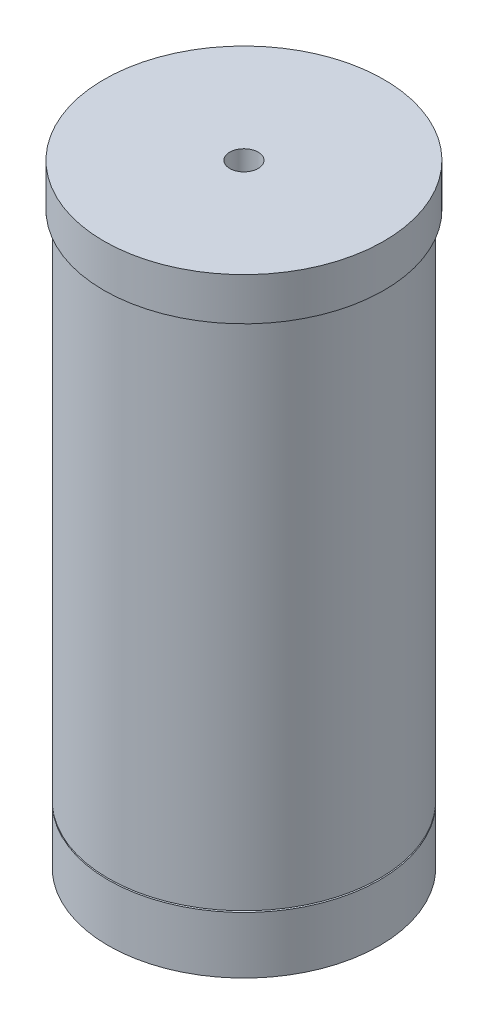
SolidWorks part; units mm, degrees
other "Bulkhead"
other "Tray"
other "Body"
other "Lid"
ref_plane "Front Plane" through (0, 0, 0) normal (0, 0, 1) x (1, 0, 0)
ref_plane "Top Plane" through (0, 0, 0) normal (0, 1, 0) x (1, 0, 0)
ref_plane "Right Plane" through (0, 0, 0) normal (1, 0, 0) x (0, 0, -1)
sketch "Sketch1" plane through (0, 0, 0) normal (0, 1, 0) x (1, 0, 0)
  circle A0 centre (0, 0) radius 47.75
  circle A1 centre (0, 0) radius 5
  circle A9 centre (-23.3345, 23.3345) radius 6
  circle A11 centre (-23.3345, 23.3345) radius 11.5
  circle A12 centre (-23.3345, 23.3345) radius 8.5
  circle A27 centre (8.541, 31.8756) radius 6
  circle A28 centre (8.541, 31.8756) radius 8.5
  circle A30 centre (8.541, 31.8756) radius 11.5
  circle A31 centre (31.8756, 8.541) radius 6
  circle A33 centre (31.8756, 8.541) radius 8.5
  circle A34 centre (31.8756, 8.541) radius 11.5
  circle A36 centre (23.3345, -23.3345) radius 6
  circle A37 centre (23.3345, -23.3345) radius 8.5
  circle A39 centre (23.3345, -23.3345) radius 11.5
  circle A40 centre (-8.541, -31.8756) radius 6
  circle A41 centre (-8.541, -31.8756) radius 8.5
  circle A42 centre (-8.541, -31.8756) radius 11.5
  circle A44 centre (-31.8756, -8.541) radius 6
  circle A45 centre (-31.8756, -8.541) radius 8.5
  circle A46 centre (-31.8756, -8.541) radius 11.5
  point P22 (0, 0)
  point P43 (0, 0)
  point P56 (0, 0)
  dimension "D1" = 95.5
  dimension "D2" = 10
  dimension "D3" = 33
  dimension "D5" = 2.5
  dimension "D4" = 3
  dimension "D6" = 6
extrude "Boss-Extrude1" add sketch "Sketch1" along normal blind 45 contours A0 A46 A42 A39 A34 A30 A11 A1 | A39 A37 | A37 A36 | A34 A33 | A33 A31 | A42 A41 | A41 A40 | A46 A45 | A45 A44 | A11 A12 | A12 A9 | A30 A28 | A28 A27
extrude "Cut-Extrude1" cut sketch "Sketch1<3>" along normal blind 5 contours A42 A41 | A46 A45 | A11 A12 | A30 A28 | A34 A33 | A39 A37
sketch "Sketch1<3>" plane through (0, 0, 0) normal (0, 1, 0) x (1, 0, 0) same geometry as "Sketch1"
sketch "Sketch3" plane through (0, 45, 0) normal (0, 1, 0) x (1, 0, 0)
  circle A0 centre (0, 0) radius 47.75
  circle A1 centre (0, 0) radius 5
  dimension "D1" = 95.5
extrude "Boss-Extrude2" add sketch "Sketch3" along normal blind 10
sketch "Sketch6" plane through (0, 55, 0) normal (0, 1, 0) x (1, 0, 0)
  line L4 (-10, 34.4976) -> (-10, -34.4976)
  line L6 (-15, 39.4976) -> (-15, -39.4976)
  line L8 (15, 39.4976) -> (15, -39.4976)
  line L10 (10, 34.4976) -> (10, -34.4976)
  line L12 (-9.5, 33.9976) -> (-9.5, -33.9976)
  line L14 (9.5, 33.9976) -> (9.5, -33.9976)
  line L16 (-15, 39.4976) -> (15, 39.4976) construction
  line L17 (-15, -39.4976) -> (15, -39.4976) construction
  line L18 (-10, -34.4976) -> (10, -34.4976) construction
  line L19 (-10, 34.4976) -> (10, 34.4976) construction
  line L20 (-9.5, -33.9976) -> (9.5, -33.9976) construction
  line L21 (-9.5, 33.9976) -> (9.5, 33.9976) construction
  line L22 (-5.5, 30.813) -> (-5.5, -30.813)
  line L23 (5.5, 30.813) -> (5.5, -30.813)
  circle A0 centre (0, 0) radius 49.28
  circle A1 centre (0, 0) radius 42.5
  arc A4 (-15, -39.4976) -> (15, -39.4976) centre (0, 0) ccw
  arc A5 (-10, -34.4976) -> (10, -34.4976) centre (0, 0) ccw
  arc A6 (10, 34.4976) -> (-10, 34.4976) centre (0, 0) ccw
  arc A7 (15, 39.4976) -> (-15, 39.4976) centre (0, 0) ccw
  arc A8 (-9.5, -33.9976) -> (9.5, -33.9976) centre (0, 0) ccw
  arc A9 (9.5, 33.9976) -> (-9.5, 33.9976) centre (0, 0) ccw
  arc A10 (-5.5, -30.813) -> (5.5, -30.813) centre (0, 0) ccw
  arc A11 (5.5, 30.813) -> (-5.5, 30.813) centre (0, 0) ccw
  circle M8 centre (0, 0) radius 47.75
  dimension "D1" = 85
  dimension "D2" = 84.5
  dimension "D4" = 30
  dimension "D6" = 4
  dimension "D3" = 5
  dimension "D5" = 0.5
extrude "Boss-Extrude6" add sketch "Sketch6" along normal blind 125 separate body contours L8 A7 L6 A4 A6 L10 A5 L4 | A1 M8 region at (0, 55, -41.3533) region at (-46.3994, 55, 0)
extrude "Boss-Extrude7" add sketch "Sketch6<4>" along normal blind 20 separate body contours L14 A9 L12 A8 A11 L23 A10 L22 region at (0, 55, -34.5689)
sketch "Sketch6<4>" plane through (0, 55, 0) normal (0, 1, 0) x (1, 0, 0) same geometry as "Sketch6"
ref_plane "Plane1" through (0, -0.5, 0) normal (0, 1, 0) x (1, 0, 0)
sketch "Sketch7" plane through (0, -0.5, 0) normal (0, 1, 0) x (1, 0, 0)
  circle A18 centre (-8.541, -31.8756) radius 8.75
  circle A19 centre (-8.541, -31.8756) radius 11.25
  circle A20 centre (0, 0) radius 47.75
  circle A21 centre (-31.8756, -8.541) radius 8.75
  circle A22 centre (-31.8756, -8.541) radius 11.25
  circle A23 centre (-23.3345, 23.3345) radius 8.75
  circle A24 centre (-23.3345, 23.3345) radius 11.25
  circle A31 centre (23.3345, -23.3345) radius 11.25
  circle A32 centre (23.3345, -23.3345) radius 8.75
  circle A45 centre (8.541, 31.8756) radius 8.75
  circle A46 centre (8.541, 31.8756) radius 11.25
  circle A47 centre (31.8756, 8.541) radius 8.75
  circle A48 centre (31.8756, 8.541) radius 11.25
  point P3 (0, 0)
  point P22 (0, 0)
  point P30 (0, 0)
  point P31 (2.4142, -3.0231)
  dimension "D1" = 6
extrude "Boss-Extrude8" add sketch "Sketch7" along normal blind 2 separate body contours A48 A47 | A31 A32 | A19 A18 | A46 A45 | A24 A23 | A22 A21 region at (-19.4728, -0.5, 31.8756) region at (-42.8074, -0.5, 8.541) region at (-34.2663, -0.5, -23.3345) region at (12.4027, -0.5, 23.3345) region at (-2.3908, -0.5, -31.8756) region at (20.9438, -0.5, -8.541)
extrude "Boss-Extrude9" add sketch "Sketch7<4>" against normal blind 20 contours A20 A48 A46 A31 A24 A22 A19 | A48 A47 | A47 | A46 A45 | A45 | A23 | A24 A23 | A21 | A22 A21 | A18 | A19 A18 | A32 | A31 A32 region at (-8.541, -0.5, 31.8756) region at (-19.4728, -0.5, 31.8756) region at (0, -0.5, 0) region at (-31.8756, -0.5, 8.541) region at (-42.8074, -0.5, 8.541) region at (-23.3345, -0.5, -23.3345) region at (-34.2663, -0.5, -23.3345) region at (12.4027, -0.5, 23.3345) region at (23.3345, -0.5, 23.3345) region at (8.541, -0.5, -31.8756) region at (-2.3908, -0.5, -31.8756) region at (31.8756, -0.5, -8.541) region at (20.9438, -0.5, -8.541)
sketch "Sketch7<4>" plane through (0, -0.5, 0) normal (0, 1, 0) x (1, 0, 0) same geometry as "Sketch7"
sketch "Sketch8" plane through (0, 180, 0) normal (0, 1, 0) x (1, 0, 0)
  line L2 (-9.5, 33.9976) -> (-9.5, -33.9976)
  line L4 (9.5, 33.9976) -> (9.5, -33.9976)
  circle A0 centre (0, 0) radius 49.28
  arc A1 (-9.5, -33.9976) -> (9.5, -33.9976) centre (0, 0) ccw
  arc A2 (9.5, 33.9976) -> (-9.5, 33.9976) centre (0, 0) ccw
  circle A3 centre (0, 0) radius 5
  circle M7 centre (0, 0) radius 42.5
  circle M8 centre (0, 0) radius 47.75
extrude "Boss-Extrude10" add sketch "Sketch8" along normal blind 15 separate body contours A2 L4 A1 L2 M7 | M8 M7 | L4 A2 L2 A1 A3 | A0 M8 region at (0, 180, -34.5689) region at (-47.8862, 180, 0) region at (-41.2979, 180, 0) region at (-46.3994, 180, 0)
extrude "Boss-Extrude11" add sketch "Sketch8<4>" against normal blind 25 contours L4 A2 L2 A1 A3 region at (0, 180, -34.5689)
sketch "Sketch8<4>" plane through (0, 180, 0) normal (0, 1, 0) x (1, 0, 0) same geometry as "Sketch8"
combine bodies "Combine1" operation type add bodies to combine 124 130 144 145 137 117
move or copy body "Unsupress for split view1" [suppressed] bodies to move or copy 146 copy no translate (0, -42.6262, 0) parameters "D1"=0, "D2"=42.6262, "D3"=0
move or copy body "Unsupress for split view2" [suppressed] bodies to move or copy 127 copy no translate (0, 244.6739, 0) parameters "D1"=0, "D2"=244.6739, "D3"=0
combine bodies "Combine2" operation type add bodies to combine 111 149 116
move or copy body "Unsupress for split view3" [suppressed] bodies to move or copy 115 copy no translate (0, 165.5325, 0) parameters "D1"=0, "D2"=165.5325, "D3"=0
